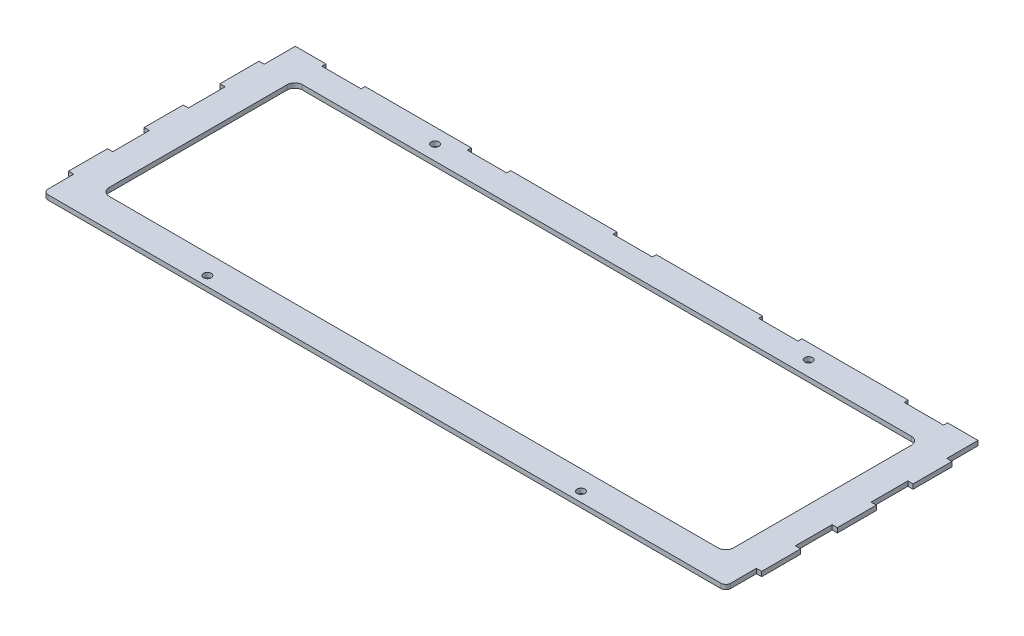
SolidWorks part; units mm, degrees
material "5052-H34"
ref_plane "Front Plane" through (0, 0, 0) normal (0, 0, 1) x (1, 0, 0)
ref_plane "Top Plane" through (0, 0, 0) normal (0, 1, 0) x (1, 0, 0)
ref_plane "Right Plane" through (0, 0, 0) normal (1, 0, 0) x (0, 0, -1)
sketch "Sketch1" plane through (0, 0, 0) normal (0, 1, 0) x (1, 0, 0)
  line L1 (-219.25, 79.3) -> (219.25, 79.3)
  line L2 (-219.25, 79.3) -> (-219.25, -79.3)
  line L3 (-215.75, -82.8) -> (215.75, -82.8)
  line L4 (219.25, 79.3) -> (219.25, -79.3)
  line L5 (-195.2, 60.25) -> (195.2, 60.25)
  line L6 (-200.2, 55.25) -> (-200.2, -58.75)
  line L7 (-195.2, -63.75) -> (195.2, -63.75)
  line L8 (200.2, 55.25) -> (200.2, -58.75)
  arc A0 (195.2, 60.25) -> (200.2, 55.25) centre (195.2, 55.25) cw
  arc A1 (195.2, -63.75) -> (200.2, -58.75) centre (195.2, -58.75) ccw
  arc A2 (-200.2, -58.75) -> (-195.2, -63.75) centre (-195.2, -58.75) ccw
  arc A3 (-195.2, 60.25) -> (-200.2, 55.25) centre (-195.2, 55.25) ccw
  arc A4 (215.75, -82.8) -> (219.25, -79.3) centre (215.75, -79.3) ccw
  arc A5 (-219.25, -79.3) -> (-215.75, -82.8) centre (-215.75, -79.3) ccw
  point P4 (0, 79.3)
  point P6 (219.25, 0)
  point P21 (219.25, -82.8)
  dimension "D7" = 5
  dimension "D8" = 3.5
  dimension "D1" = 438.5
  dimension "D2" = 162.1
  dimension "D3" = 19.05
  dimension "D4" = 19.05
  dimension "D5" = 19.05
  dimension "D6" = 19.05
base flange "Base-Flange1" sketch "Sketch1" thickness 3 reverse thickness direction no parameters "D1"=0.7366
sketch "Sketch7" plane through (0, -3, 0) normal (0, -1, 0) x (1, 0, 0)
  line L2 (174.35, -76.95) -> (174.35, -79.3) construction
  line L3 (199.15, -76.8) -> (199.15, -79.3) construction
  line L4 (219.25, -79.3) -> (-219.25, -79.3) construction
  line L5 (174.15, -79.3) -> (199.35, -79.3)
  line L6 (174.15, -79.3) -> (174.15, -76.75)
  line L7 (174.15, -76.75) -> (199.35, -76.75)
  line L8 (199.35, -79.3) -> (199.35, -76.75)
  line L9 (80.775, -79.3) -> (80.775, -76.75)
  line L10 (80.775, -76.75) -> (105.975, -76.75)
  line L11 (80.775, -79.3) -> (105.975, -79.3)
  line L12 (105.975, -79.3) -> (105.975, -76.75)
  line L13 (-12.6, -79.3) -> (-12.6, -76.75)
  line L14 (-12.6, -76.75) -> (12.6, -76.75)
  line L15 (-12.6, -79.3) -> (12.6, -79.3)
  line L16 (12.6, -79.3) -> (12.6, -76.75)
  line L17 (-105.975, -79.3) -> (-105.975, -76.75)
  line L18 (-105.975, -76.75) -> (-80.775, -76.75)
  line L19 (-105.975, -79.3) -> (-80.775, -79.3)
  line L20 (-80.775, -79.3) -> (-80.775, -76.75)
  line L21 (-199.35, -79.3) -> (-199.35, -76.75)
  line L22 (-199.35, -76.75) -> (-174.15, -76.75)
  line L23 (-199.35, -79.3) -> (-174.15, -79.3)
  line L24 (-174.15, -79.3) -> (-174.15, -76.75)
  dimension "D1" = 0.2
  dimension "D2" = 0.2
  dimension "D3" = 0.2
  dimension "D4" = 5
extrude "Cut-Extrude1" cut sketch "Sketch7" against normal blind 10 normal cut yes
sketch "Sketch8" plane through (0, -3, 0) normal (0, -1, 0) x (1, 0, 0)
  line L0 (-219.25, -79.3) -> (-219.25, 79.3) construction
  line L1 (-219.25, -59.3) -> (-222.25, -59.3)
  line L2 (-219.25, -59.3) -> (-219.25, -34.3)
  line L3 (-219.25, -34.3) -> (-222.25, -34.3)
  line L4 (-222.25, -59.3) -> (-222.25, -34.3)
  line L5 (-199.35, -79.3) -> (-219.25, -79.3) construction
  line L6 (-222.25, -10.75) -> (-222.25, 14.25)
  line L7 (-219.25, -10.75) -> (-222.25, -10.75)
  line L8 (-219.25, -10.75) -> (-219.25, 14.25)
  line L9 (-219.25, 14.25) -> (-222.25, 14.25)
  line L10 (-222.25, 37.8) -> (-222.25, 62.8)
  line L11 (-219.25, 37.8) -> (-222.25, 37.8)
  line L12 (-219.25, 37.8) -> (-219.25, 62.8)
  line L13 (-219.25, 62.8) -> (-222.25, 62.8)
  dimension "D1" = 3
  dimension "D2" = 25
  dimension "D3" = 20
  dimension "D4" = 3
extrude "Boss-Extrude1" add sketch "Sketch8" against normal up to surface (3 mm away) contours L10 L13 L12 L11 | L6 L9 L8 L7 | L2 L3 L4 L1 up to face at (0, 0, -53.5942)
sketch "Sketch9" plane through (0, -3, 0) normal (0, -1, 0) x (1, 0, 0)
  line L0 (-199.35, -79.3) -> (-219.25, -79.3) construction
  line L1 (-219.25, -59.3) -> (-218.9, -59.3)
  line L2 (-219.25, -59.3) -> (-219.25, -79.3)
  line L3 (-219.25, -79.3) -> (-218.9, -79.3)
  line L4 (-218.9, -59.3) -> (-218.9, -79.3)
  line L5 (-219.25, -59.3) -> (-222.25, -59.3) construction
  line L6 (-219.25, -10.75) -> (-218.9, -10.75)
  line L7 (-219.25, -10.75) -> (-219.25, -34.3)
  line L8 (-219.25, -34.3) -> (-218.9, -34.3)
  line L9 (-218.9, -10.75) -> (-218.9, -34.3)
  line L10 (-219.25, 37.8) -> (-218.9, 37.8)
  line L11 (-219.25, 37.8) -> (-219.25, 14.25)
  line L12 (-219.25, 14.25) -> (-218.9, 14.25)
  line L13 (-218.9, 37.8) -> (-218.9, 14.25)
  line L14 (-219.25, -34.3) -> (-222.25, -34.3) construction
  line L15 (-219.25, 14.25) -> (-222.25, 14.25) construction
  dimension "D1" = 0.35
  dimension "D2" = 0.35
  dimension "D3" = 0.35
extrude "Cut-Extrude2" cut sketch "Sketch9" against normal blind 4.55 normal cut yes
mirror "Mirror1" about plane through (0, 0, 0) normal (1, 0, 0) of "Cut-Extrude2", "Boss-Extrude1"
sketch "Sketch10" plane through (0, -3, 0) normal (0, -1, 0) x (1, 0, 0)
  line L0 (219.25, 79.3) -> (219.25, 62.8) construction
  line L1 (-215.75, 82.8) -> (215.75, 82.8) construction
  line L2 (-219.25, 62.8) -> (-219.25, 79.3) construction
  line L3 (219.25, 79.3) -> (219.25, 62.8)
  line L4 (-215.75, 82.8) -> (215.75, 82.8)
  line L5 (-219.25, 62.8) -> (-219.25, 79.3)
  line L6 (-218.9, 62.8) -> (-218.9, 79.3)
  line L7 (-215.75, 82.45) -> (215.75, 82.45)
  line L8 (218.9, 79.3) -> (218.9, 62.8)
  line L9 (-219.25, 62.8) -> (-218.9, 62.8)
  line L10 (219.25, 62.8) -> (218.9, 62.8)
  arc A0 (219.25, 79.3) -> (215.75, 82.8) centre (215.75, 79.3) ccw construction
  arc A1 (-215.75, 82.8) -> (-219.25, 79.3) centre (-215.75, 79.3) ccw construction
  arc A2 (219.25, 79.3) -> (215.75, 82.8) centre (215.75, 79.3) ccw
  arc A3 (-215.75, 82.8) -> (-219.25, 79.3) centre (-215.75, 79.3) ccw
  arc A4 (-215.75, 82.45) -> (-218.9, 79.3) centre (-215.75, 79.3) ccw
  arc A5 (218.9, 79.3) -> (215.75, 82.45) centre (215.75, 79.3) ccw
  dimension "D1" = 0.35
extrude "Cut-Extrude3" cut sketch "Sketch10" against normal blind 4.55 normal cut yes
sketch "Sketch11" plane through (0, -3, 0) normal (0, -1, 0) x (1, 0, 0)
  circle A4 centre (-119.741, 76.275) radius 2.5
  circle A5 centre (-119.741, -69.775) radius 2.5
  circle A6 centre (119.8609, -69.775) radius 2.5
  circle A7 centre (119.8609, 76.275) radius 2.5
extrude "Cut-Extrude4" cut sketch "Sketch11" against normal through all normal cut yes
sketch "Bend-Lines1" [suppressed] plane through (0, 0, 0) normal (0, 1, 0) x (1, 0, 0)
sketch "Bounding-Box1" [suppressed] plane through (0, 0, 0) normal (0, 1, 0) x (1, 0, 0)
sheet metal parameters "Sheet-Metal1" thickness 3 parameters "D1"=0.7366
flat pattern "Flat-Pattern1" [suppressed]
sketch "Bend-Lines2" plane through (0, 0, 0) normal (0, 1, 0) x (1, 0, 0)
sketch3d "Bounding-Box2" [suppressed]
  line L0 (-3.5, -3.4994, 0) -> (435, -3.5, 0) construction
  line L1 (-3.4998, 158.6, 0) -> (435.0002, 158.5994, 0) construction
  line L2 (-3.5, -3.4994, 0) -> (-3.4998, 158.6, 0) construction
  line L3 (435, -3.5, 0) -> (435.0002, 158.5994, 0) construction
sheet metal parameters "Sheet-Metal2" thickness 3 parameters "D1"=0.7366
flat pattern "Flat-Pattern1"
sketch "Bend-Lines2" plane through (0, 0, 0) normal (0, 1, 0) x (1, 0, 0)
sketch3d "Bounding-Box2" [suppressed]
  line L0 (-3.5, -3.4994, 0) -> (435, -3.5, 0) construction
  line L1 (-3.4998, 158.6, 0) -> (435.0002, 158.5994, 0) construction
  line L2 (-3.5, -3.4994, 0) -> (-3.4998, 158.6, 0) construction
  line L3 (435, -3.5, 0) -> (435.0002, 158.5994, 0) construction
sheet metal parameters "Sheet-Metal3" thickness 3 parameters "D1"=0.7366
flat pattern "Flat-Pattern1"
sketch "Bend-Lines2" plane through (0, 0, 0) normal (0, 1, 0) x (1, 0, 0)
sketch3d "Bounding-Box2" [suppressed]
  line L0 (-6.5, -3.4994, 0) -> (435, -3.5, 0) construction
  line L1 (-6.4998, 158.6, 0) -> (435.0002, 158.5994, 0) construction
  line L2 (-6.5, -3.4994, 0) -> (-6.4998, 158.6, 0) construction
  line L3 (435, -3.5, 0) -> (435.0002, 158.5994, 0) construction
sheet metal parameters "Sheet-Metal4" thickness 3 parameters "D1"=0.7366
flat pattern "Flat-Pattern1"
sketch "Bend-Lines2" plane through (0, 0, 0) normal (0, 1, 0) x (1, 0, 0)
sketch3d "Bounding-Box2" [suppressed]
  line L0 (-6.5, -3.4994, 0) -> (435, -3.5, 0) construction
  line L1 (-6.4998, 158.6, 0) -> (435.0002, 158.5994, 0) construction
  line L2 (-6.5, -3.4994, 0) -> (-6.4998, 158.6, 0) construction
  line L3 (435, -3.5, 0) -> (435.0002, 158.5994, 0) construction
sheet metal parameters "Sheet-Metal5" thickness 3 parameters "D1"=0.7366
flat pattern "Flat-Pattern1"
sketch "Bend-Lines2" plane through (0, 0, 0) normal (0, 1, 0) x (1, 0, 0)
sketch3d "Bounding-Box2" [suppressed]
  line L0 (-6.5, -3.4994, 0) -> (438, -3.5, 0) construction
  line L1 (-6.4998, 158.6, 0) -> (438.0002, 158.5994, 0) construction
  line L2 (-6.5, -3.4994, 0) -> (-6.4998, 158.6, 0) construction
  line L3 (438, -3.5, 0) -> (438.0002, 158.5994, 0) construction
sheet metal parameters "Sheet-Metal6" thickness 3 parameters "D1"=0.7366
flat pattern "Flat-Pattern1"
sketch "Bend-Lines2" plane through (0, 0, 0) normal (0, 1, 0) x (1, 0, 0)
sketch3d "Bounding-Box2" [suppressed]
  line L0 (438, -3.375, 0) -> (-6.5, -3.375, 0) construction
  line L1 (438, 158.6, 0) -> (-6.5, 158.6, 0) construction
  line L2 (438, -3.375, 0) -> (438, 158.6, 0) construction
  line L3 (-6.5, -3.375, 0) -> (-6.5, 158.6, 0) construction
sheet metal parameters "Sheet-Metal9" thickness 3 parameters "D1"=0.7366
flat pattern "Flat-Pattern1"
sketch "Bend-Lines2" plane through (0, 0, 0) normal (0, 1, 0) x (1, 0, 0)
sketch3d "Bounding-Box2" [suppressed]
  line L0 (438, -3.15, 0) -> (-6.5, -3.15, 0) construction
  line L1 (438, 158.6, 0) -> (-6.5, 158.6, 0) construction
  line L2 (438, -3.15, 0) -> (438, 158.6, 0) construction
  line L3 (-6.5, -3.15, 0) -> (-6.5, 158.6, 0) construction
